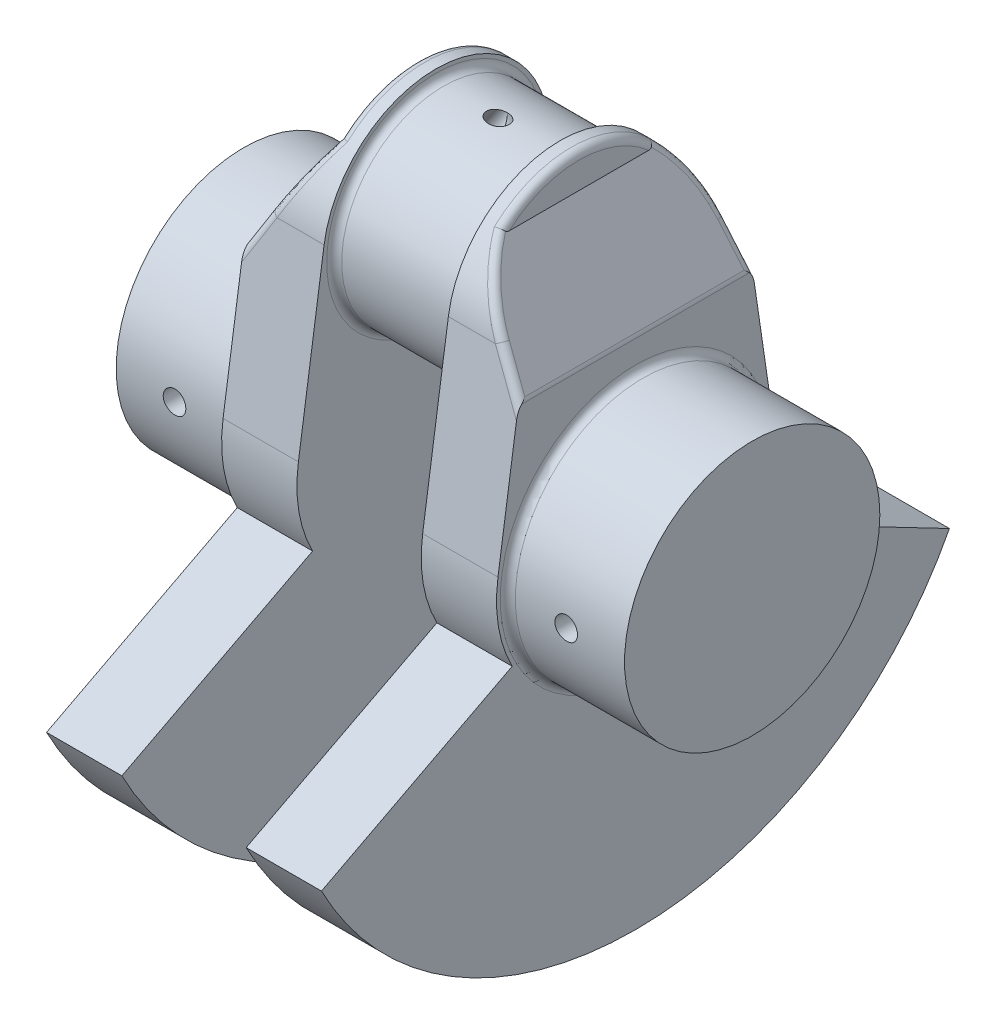
SolidWorks part; units mm, degrees
ref_plane "Спереди" through (0, 0, 0) normal (0, 0, 1) x (1, 0, 0)
ref_plane "Сверху" through (0, 0, 0) normal (0, 1, 0) x (1, 0, 0)
ref_plane "Справа" through (0, 0, 0) normal (1, 0, 0) x (0, 0, -1)
sketch "Эскиз3" plane through (0, 0, 0) normal (1, 0, 0) x (0, 0, -1)
  circle A0 centre (0, 0) radius 33.9
  dimension "D1" = 67.8
extrude "Бобышка-Вытянуть1" add sketch "Эскиз3" along normal blind 31 contours A0
sketch "Эскиз4" plane through (31, 0, 0) normal (1, 0, 0) x (0, 0, -1)
  line L0 (-29.6818, 51.8579) -> (-36.5086, 5.3602)
  line L1 (29.6818, 51.8579) -> (36.5086, 5.3602)
  line L2 (-83.379, -43.4044) -> (0, 0)
  line L3 (0, -47) -> (0, 0)
  line L4 (83.379, -43.4044) -> (0, 0)
  circle A0 centre (0, 0) radius 36.9
  circle A1 centre (0, 47.5) radius 30
  circle A2 centre (0, 0) radius 33.9 construction
  arc A3 (83.379, -43.4044) -> (-83.379, -43.4044) centre (0, 0) cw
  circle M1 centre (0, 0) radius 33.9
  dimension "D1" = 47.5
  dimension "D2" = 60
  dimension "D4" = 94
  dimension "D3" = 3
  dimension "D5" = 117.5
extrude "Бобышка-Вытянуть2" add sketch "Эскиз4" along normal blind 20 contours A1 A0 | A0 A1 M1 | A1 M1 | A1 A0 L1 | A1 A0 M1 | A1 M1 | A1 L0 A0 | A0 | L4 A3 L2 region at (31, 28.8579, 30.213) region at (31, 53.1931, 0) region at (31, 28.8579, -30.213) region at (31, 36.4222, 0) region at (31, 2.6521, -36.3209) region at (31, 25.8071, 0) region at (31, 5.6798, 0)
sketch "Эскиз6" plane through (0, 0, 0) normal (0, 0, 1) x (1, 0, 0)
  line L0 (31, 77.5) -> (46, 77.5)
  line L1 (51, 77.5) -> (31, 77.5) construction
  line L2 (46, 77.5) -> (46, 68.5)
  line L3 (46, 68.5) -> (31, 42.5192)
  line L4 (31, 77.5) -> (31, 51.8579) construction
  line L5 (31, 42.5192) -> (31, 77.5)
  dimension "D1" = 5
  dimension "D2" = 60
  dimension "D3" = 9
extrude "Вырез-Вытянуть1" cut sketch "Эскиз6" against normal through all and the other way through all
fillet "Скругление1" radius 2 6 edges at (31, 42.5192, 0) (33.6958, 47.1886, -30.3673) (41.5742, 60.8343, -26.8737) (33.6958, 47.1886, 30.3673) (41.5742, 60.8343, 26.8737) (46, 77.5, 0)
sketch "Эскиз5" plane through (51, 0, 0) normal (1, 0, 0) x (0, 0, -1)
  circle A1 centre (0, 47.5) radius 27
  dimension "D1" = 54
  dimension "D2" = 47.5
extrude "Бобышка-Вытянуть3" add sketch "Эскиз5" along normal blind 16.5
fillet "Скругление2" radius 2 1 edges at (51, 47.5, -27)
fillet "Скругление3" radius 2 1 edges at (31, 0, -33.9)
sketch "Эскиз8" plane through (0, 0, 0) normal (0, 0, 1) x (1, 0, 0)
  line L0 (0, 33.9) -> (31, 33.9)
  line L1 (31, 38.8098) -> (31, 5.3602) construction
  circle A0 centre (15.5, 0) radius 3
  dimension "D1" = 6
extrude "Вырез-Вытянуть2" cut sketch "Эскиз8" against normal through all both and the other way through all contours A0
ref_axis "Ось1" through (67.5, -102.575, 0) along (0, 1, 0)
ref_plane "Плоскость2" through (0, 74.5, 0) normal (0, 1, 0) x (1, 0, 0)
ref_point "Точка1"
ref_axis "Ось3" through (15.5, 0, -33.9) along (0, 0, 1)
ref_point "Точка2"
ref_axis "Ось4" through (15.5, 0, 0) along (0.5724, 0.82, 0)
ref_plane "Плоскость5" through (67.5, 74.5, 0) normal (0.5724, 0.82, 0) x (0.82, -0.5724, 0)
sketch "Эскиз10" plane through (67.5, 74.5, 0) normal (0.5724, 0.82, 0) x (0.82, -0.5724, 0)
  circle A0 centre (0, 0) radius 2.5
  dimension "D1" = 5
extrude "Вырез-Вытянуть3" cut sketch "Эскиз10" against normal up to next
mirror "Зеркальное отражение5" about plane through (67.5, 47.5, 0) normal (1, 0, 0) of "Вырез-Вытянуть3", "Скругление3", "Скругление2", "Бобышка-Вытянуть3", "Скругление1", "Вырез-Вытянуть1", "Бобышка-Вытянуть2", "Бобышка-Вытянуть1", "Вырез-Вытянуть2"
